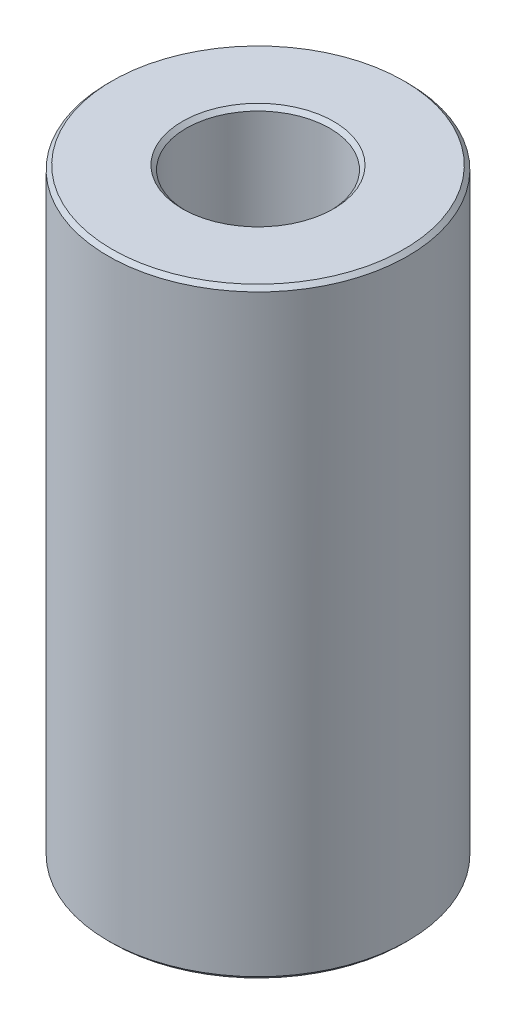
SolidWorks part; units mm, degrees
ref_plane "Front Plane" through (0, 0, 0) normal (0, 0, 1) x (1, 0, 0)
ref_plane "Top Plane" through (0, 0, 0) normal (0, 1, 0) x (1, 0, 0)
ref_plane "Right Plane" through (0, 0, 0) normal (1, 0, 0) x (0, 0, -1)
sketch "Sketch1" plane through (0, 0, 0) normal (0, 1, 0) x (1, 0, 0)
  circle A0 centre (0, 0) radius 55
  dimension "SLEEVE_OD" = 110
extrude "Boss-Extrude1" add sketch "Sketch1" along normal blind 220.5694
sketch "Sketch2" plane through (0, 0, 0) normal (0, 1, 0) x (1, 0, 0)
  circle A0 centre (0, 0) radius 26.3505
  dimension "BORE_D" = 52.701
extrude "Cut-Extrude1" cut sketch "Sketch2" along normal through all
chamfer "Chamfer1" distance 1.444 angle 45 4 edges at (0, 220.5694, 26.3505) (0, 0, 26.3505) (0, 0, 55) (0, 220.5694, 55)
